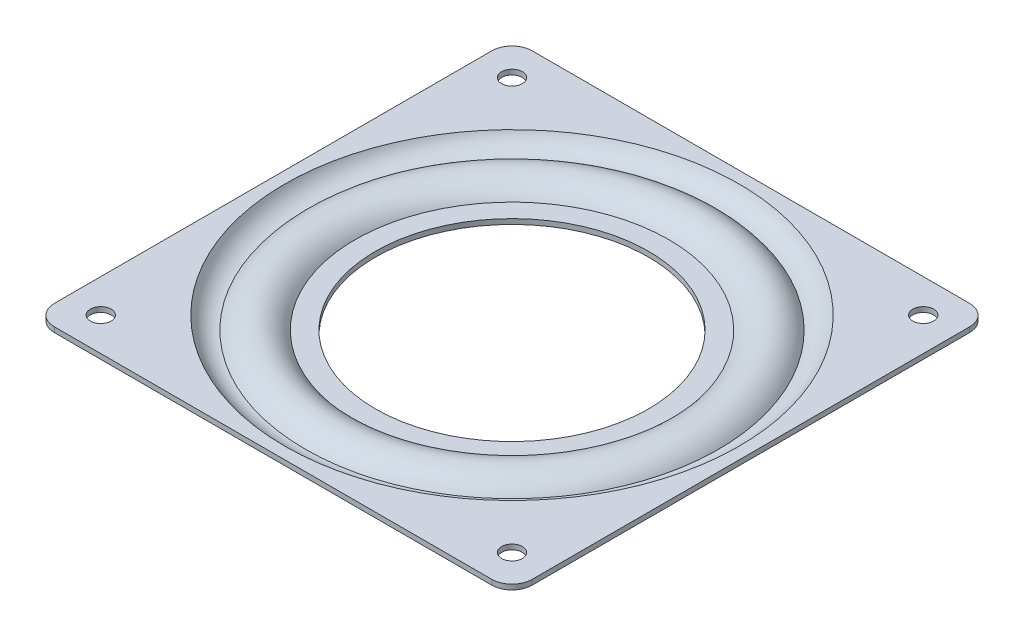
SolidWorks part; units mm, degrees
material "6061-T6 (SS)"
ref_plane "前视基准面" through (0, 0, 0) normal (0, 0, 1) x (1, 0, 0)
ref_plane "上视基准面" through (0, 0, 0) normal (0, 1, 0) x (1, 0, 0)
ref_plane "右视基准面" through (0, 0, 0) normal (1, 0, 0) x (0, 0, -1)
sketch "草图1" plane through (0, 0, 0) normal (0, 0, 1) x (1, 0, 0)
  line L0 (-36.7805, 0) -> (-35.9228, 0)
  line L1 (0, 6.9172) -> (0, -6.9172) construction
  line L2 (-31, -2.5698) -> (-27, -2.5698)
  line L3 (-35.9228, 0) -> (0, 0) construction
  line L4 (0, 0) -> (43.3864, 0) construction
  line L5 (-43.3864, 0) -> (-36.7805, 0) construction
  line L6 (-31.5531, -3.5698) -> (-27, -3.5698)
  line L7 (-27, -2.5698) -> (-27, -3.5698)
  line L8 (-44.9105, 0) -> (-45.8139, -0.4289)
  arc A0 (-44.9105, 0) -> (-40.8455, -2.5698) centre (-40.8455, 1.9302) ccw
  arc A1 (-40.8455, -2.5698) -> (-31, -2.5698) centre (-35.9228, -6) cw
  arc A2 (-40.8455, -2.5698) -> (-36.8127, -0.0664) centre (-40.8455, 1.9302) ccw construction
  arc A3 (-36.8127, -0.0664) -> (-36.7805, 0) centre (-40.8455, 1.9302) ccw
  arc A4 (-45.8139, -0.4289) -> (-40.2759, -3.5402) centre (-40.8455, 1.9302) ccw
  arc A5 (-40.2759, -3.5402) -> (-31.5531, -3.5698) centre (-35.9228, -6) cw
  point P4 (0, 0)
  point P8 (0, 0)
  dimension "D1" = 4.5
  dimension "D2" = 6
  dimension "D3" = 27
  dimension "D4" = 4
revolve "旋转1" add sketch "草图1" angle 360 about L1 region at (-33.2348, -0.8509, 0)
sketch "草图2" plane through (0, 0, 0) normal (0, 1, 0) x (1, 0, 0)
  line L0 (0, 0) -> (-40.6586, 40.6586) construction
  line L1 (-43.25, 47.25) -> (47.25, 47.25)
  line L2 (-47.25, 43.25) -> (-47.25, -47.25)
  line L3 (-47.25, -47.25) -> (47.25, -47.25)
  line L4 (47.25, 47.25) -> (47.25, -47.25)
  line L5 (-47.25, 47.25) -> (47.25, -47.25) construction
  line L6 (-47.25, -47.25) -> (47.25, 47.25) construction
  line L7 (0, 0) -> (40.6586, 40.6586) construction
  line L8 (0, 0) -> (-43.25, 43.25) construction
  circle A0 centre (0, 0) radius 44.9105 construction
  circle A1 centre (0, 0) radius 44.9105
  arc A2 (-43.25, 47.25) -> (-47.25, 43.25) centre (-43.25, 43.25) ccw
  circle A3 centre (-40.6586, 40.6586) radius 2.05
  circle A4 centre (40.6586, 40.6586) radius 2.05
  circle A5 centre (40.6586, -40.6586) radius 2.05
  circle A6 centre (-40.6586, -40.6586) radius 2.05
  arc A7 (47.25, 43.25) -> (43.25, 47.25) centre (43.25, 43.25) ccw
  arc A8 (43.25, -47.25) -> (47.25, -43.25) centre (43.25, -43.25) ccw
  arc A9 (-47.25, -43.25) -> (-43.25, -47.25) centre (-43.25, -43.25) ccw
  dimension "D3" = 4
  dimension "D4" = 4.1
  dimension "D9" = 4
  dimension "D1" = 94.5
  dimension "D2" = 94.5
  dimension "D5" = 57.5
  dimension "D7" = 90
  dimension "D8" = 57.5
  dimension "D10" = 61.1647
  dimension "D6" = 4
extrude "凸台-拉伸1" add sketch "草图2" against normal blind 1 contours L2 A9 L3 A8 L4 A7 L1 A2 A6 A5 A4 A3 A1 region at (0, 0, -45.9136)
ref_axis "Axis1" through (0, -40.6526, 0) along (0, 1, 0)
